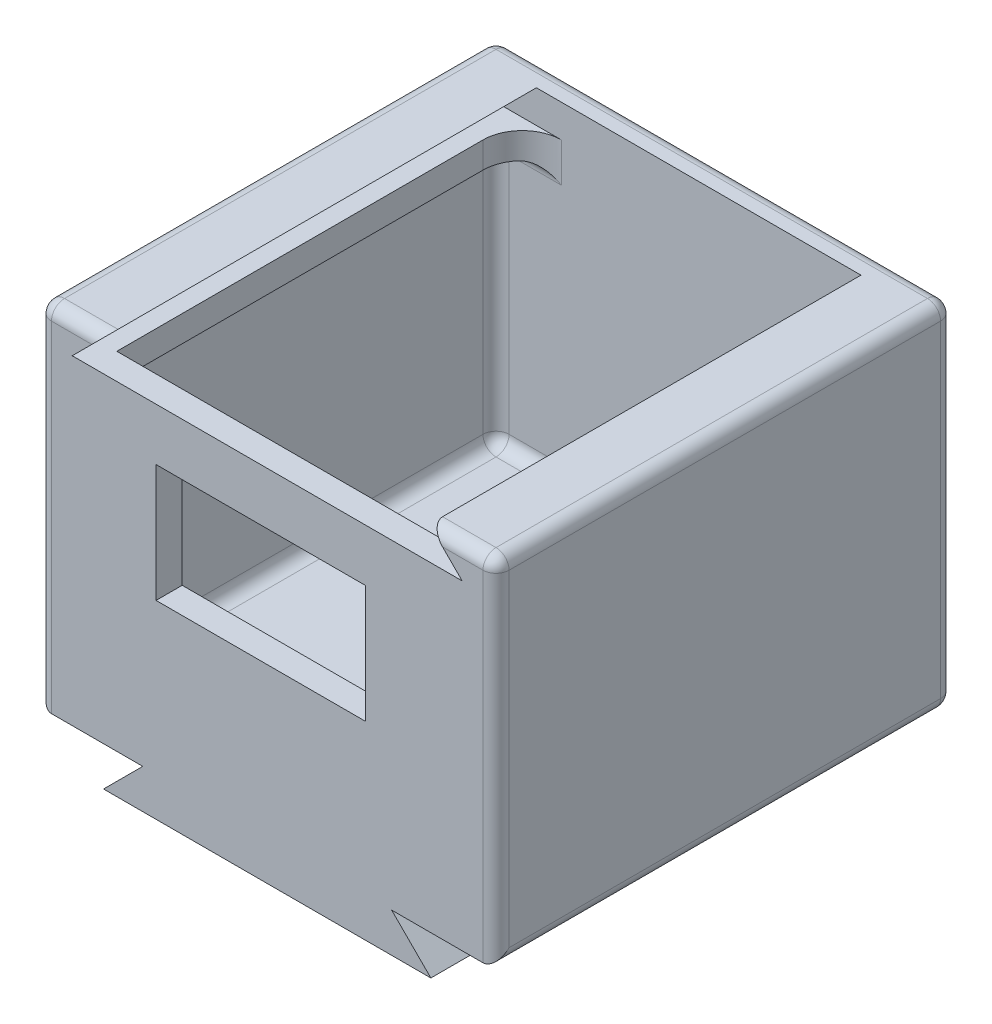
SolidWorks part; units mm, degrees
other "Markup1"
sketch "Sketch14" plane through (16, 27, 17.5) normal (0.8475, 0.408, 0.3394) x (0.3204, 0.1164, -0.9401)
ref_plane "Front Plane" through (0, 0, 0) normal (0, 0, 1) x (1, 0, 0)
ref_plane "Top Plane" through (0, 0, 0) normal (0, 1, 0) x (1, 0, 0)
ref_plane "Right Plane" through (0, 0, 0) normal (1, 0, 0) x (0, 0, -1)
sketch "Sketch1" plane through (0, 0, 0) normal (0, 1, 0) x (1, 0, 0)
  line L1 (-17.5, -17.5) -> (17.5, -17.5)
  line L2 (-17.5, -17.5) -> (-17.5, 17.5)
  line L3 (-17.5, 17.5) -> (17.5, 17.5)
  line L4 (17.5, -17.5) -> (17.5, 17.5)
  line L5 (-17.5, -17.5) -> (17.5, 17.5) construction
  line L6 (-17.5, 17.5) -> (17.5, -17.5) construction
  point P0 (0, 0)
  dimension "D1" = 35
  dimension "D2" = 35
extrude "Boss-Extrude1" add sketch "Sketch1" along normal blind 27
shell "Shell1" thickness 2 removed face at (0, 27, 0)
sketch "Sketch5" plane through (0, 0, 17.5) normal (0, 0, 1) x (1, 0, 0)
  line L0 (-14.5, 27) -> (-14.5, 25.2657) construction
  line L1 (-17.5, 27) -> (17.5, 27) construction
  line L2 (14.5, 27) -> (14.5, 25.2657) construction
  line L3 (-17.5, 27) -> (-17.5, 0) construction
  line L4 (-12.4121, 27) -> (12.4121, 27)
  line L5 (-12.5157, 27.25) -> (-15.5157, 24.25) construction
  line L6 (12.5157, 27.25) -> (15.5157, 24.25) construction
  line L7 (-15.5157, 24.25) -> (15.5157, 24.25) construction
  line L8 (-12.5157, 27.25) -> (12.5157, 27.25) construction
  line L9 (12.4121, 27) -> (14.9121, 24.5)
  line L10 (-14.9121, 24.5) -> (14.9121, 24.5)
  line L11 (-12.4121, 27) -> (-14.9121, 24.5)
  dimension "D1" = 45
  dimension "D2" = 3
  dimension "D3" = 3
  dimension "D4" = 2
  dimension "D5" = 45
  dimension "D6" = 0.25
  dimension "D7" = 2
  dimension "D8" = 3
extrude "Cut-Extrude7" cut sketch "Sketch5" against normal up to surface (33 mm away) up to face at (0, 14.5, -15.5)
sketch "Sketch16" plane through (0, 0, 15.5) normal (0, 0, -1) x (-1, 0, 0)
  line L0 (-15.5, 27) -> (-12.4121, 27)
  line L1 (-12.4121, 27) -> (-14.9121, 24.5)
  line L2 (-14.9121, 24.5) -> (-13.5, 24.5)
  line L3 (-14.9121, 24.5) -> (14.9121, 24.5) construction
  line L4 (-13.5, 24.5) -> (-13.5, 22.5)
  line L5 (-13.5, 22.5) -> (-15.5, 22.5)
  line L6 (-15.5, 27) -> (-15.5, 2) construction
  line L7 (-15.5, 22.5) -> (-15.5, 27)
  line L8 (0, 24.5) -> (0, 25.5) construction
  line L9 (13.5, 22.5) -> (15.5, 22.5)
  line L10 (13.5, 24.5) -> (13.5, 22.5)
  line L11 (14.9121, 24.5) -> (13.5, 24.5)
  line L12 (12.4121, 27) -> (14.9121, 24.5)
  line L13 (15.5, 27) -> (12.4121, 27)
  line L14 (15.5, 22.5) -> (15.5, 27)
  dimension "D1" = 1
  dimension "D2" = 2
  dimension "D3" = 2
extrude "Boss-Extrude4" add sketch "Sketch16" along normal up to surface (31 mm away) up to face at (0, 14.5, -15.5)
sketch "Sketch9" plane through (0, 0, 17.5) normal (0, 0, 1) x (1, 0, 0)
  line L0 (-9.8, 0) -> (-13, -3.2) construction
  line L1 (-17.5, 0) -> (17.5, 0) construction
  line L2 (-13, -3.2) -> (13, -3.2) construction
  line L3 (13, -3.2) -> (9.8, 0) construction
  line L4 (9.8, 0) -> (-9.8, 0) construction
  line L5 (-9.5172, 0) -> (-12.5172, -3)
  line L6 (-12.5172, -3) -> (12.5172, -3)
  line L7 (12.5172, -3) -> (9.5172, 0)
  line L8 (9.5172, 0) -> (-9.5172, 0)
  point P4 (0, -3.2)
  dimension "D1" = 26
  dimension "D2" = 45
  dimension "D3" = 45
  dimension "D4" = 3
  dimension "D5" = 0.2
  dimension "D6" = 0.2
  dimension "D7" = 0.2
extrude "Boss-Extrude3" add sketch "Sketch9" against normal blind 26 contours L8 L5 L6 L7
fillet "Fillet1" radius 1 8 edges at (-15.5, 12.25, 15.5) (15.5, 12.25, -15.5) (15.5, 12.25, 15.5) (0, 2, 15.5) (15.5, 2, 0) (0, 2, -15.5) (-15.5, 2, 0) (-15.5, 12.25, -15.5)
fillet "Fillet2" radius 1 8 edges at (17.5, 13.5, 17.5) (17.5, 27, 0) (17.5, 13.5, -17.5) (17.5, 0, 0) (-17.5, 13.5, -17.5) (-17.5, 27, 0) (-17.5, 13.5, 17.5) (-17.5, 0, 0)
fillet "Fillet3" radius 1 6 edges at (17.2071, 26.7071, -17.2071) (-17.2071, 26.7071, -17.2071) (17.2071, 0.2929, -17.2071) (-17.2071, 0.2929, -17.2071) (0, 27, -17.5) (0, 0, -17.5)
fillet "Fillet4" radius 1 4 edges at (17.2071, 26.7071, 17.2071) (-17.2071, 26.7071, 17.2071) (14.4561, 27, 17.5) (-14.4561, 27, 17.5)
sketch "Sketch10" plane through (0, 2, 0) normal (0, 1, 0) x (1, 0, 0)
  line L1 (10, -14.5) -> (-10, -14.5) construction
  line L2 (10, -14.5) -> (10, 10.5) construction
  line L3 (10, 10.5) -> (-10, 10.5) construction
  line L4 (-10, -14.5) -> (-10, 10.5) construction
  line L5 (10, -14.5) -> (-10, 10.5) construction
  line L6 (10, 10.5) -> (-10, -14.5) construction
  line L8 (-14.5, -14.5) -> (14.5, -14.5) construction
  circle A0 centre (-7.5, -9.5) radius 1.65
  circle A1 centre (7.5, -9.5) radius 1.65
  point P0 (0, -2)
  dimension "D3" = 3.3
  dimension "D1" = 20
  dimension "D2" = 25
  dimension "D4" = 2.5
  dimension "D5" = 5
  dimension "D6" = 2.5
  dimension "D7" = 0
extrude "Cut-Extrude3" cut sketch "Sketch10" against normal through all
sketch "Sketch11" plane through (0, 0, 17.5) normal (0, 0, -1) x (-1, 0, 0)
  line L0 (-16.5, 1) -> (16.5, 1) construction
  line L1 (8.5, 11.5) -> (-7.5, 11.5)
  line L2 (8.5, 11.5) -> (8.5, 20.5)
  line L3 (8.5, 20.5) -> (-7.5, 20.5)
  line L4 (-7.5, 11.5) -> (-7.5, 20.5)
  line L5 (8.5, 11.5) -> (-7.5, 20.5) construction
  line L6 (8.5, 20.5) -> (-7.5, 11.5) construction
  line L9 (16.5, 1) -> (16.5, 26) construction
  point P0 (0.5, 16)
  dimension "D1" = 9
  dimension "D2" = 16
  dimension "D3" = 15
  dimension "D4" = 16
extrude "Cut-Extrude4" cut sketch "Sketch11" against normal up to surface (-33 mm away) up to face at (0, 20.6667, -15.5)
sketch "Sketch13" plane through (0, -3, 0) normal (0, -1, 0) x (1, 0, 0)
  circle A0 centre (-7.5, 9.5) radius 2.6
  circle A1 centre (7.5, 9.5) radius 2.6
  dimension "D1" = 5.2
  dimension "D2" = 5.2
extrude "Cut-Extrude6" cut sketch "Sketch13" against normal blind 2
fillet "Fillet5" radius 3 2 edges at (-13.5, 23.5, -15.5) (13.5, 23.5, -15.5)
fillet "Fillet6" radius 1 10 edges at (12.5, 22.5, -15.5) (15.2071, 22.5, -15.2071) (14, 22.5, 15.5) (15.2071, 22.5, 15.2071) (-12.5, 22.5, -15.5) (-15.2071, 22.5, -15.2071) (-14, 22.5, 15.5) (-15.2071, 22.5, 15.2071) (15.5, 22.5, 0) (-15.5, 22.5, 0)
